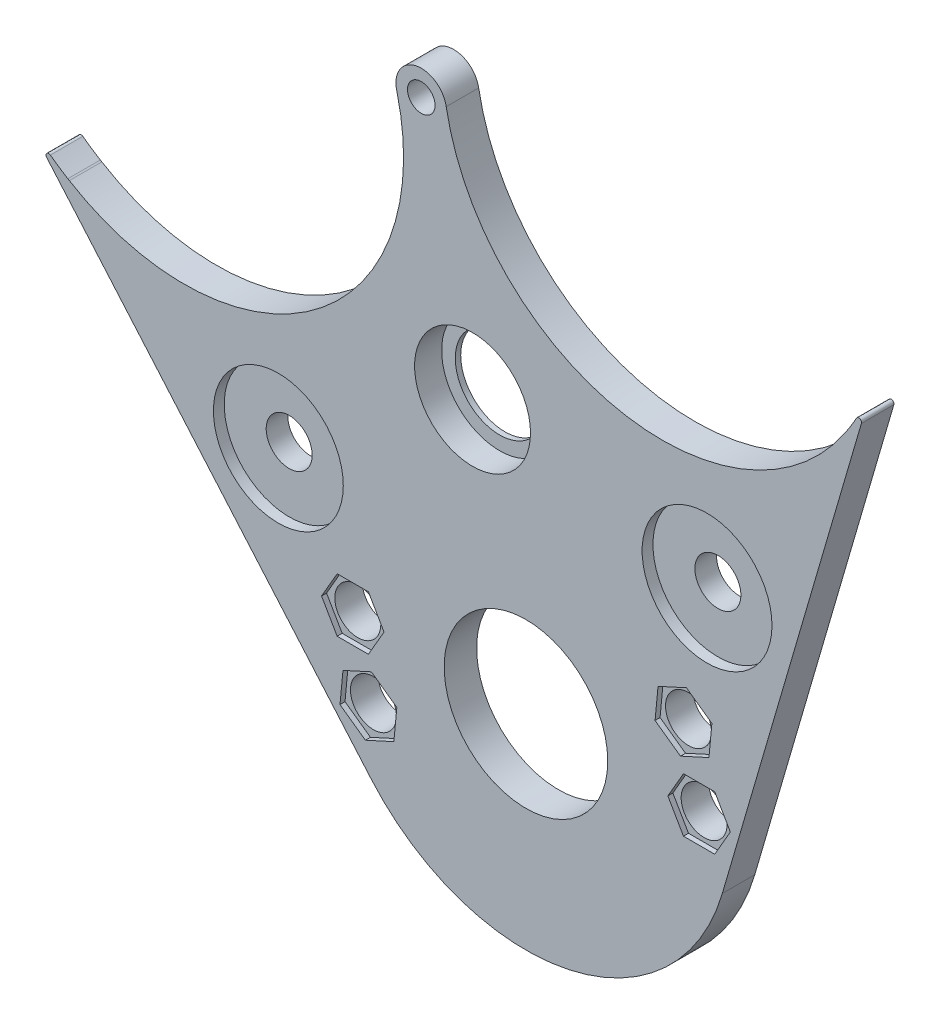
SolidWorks part; units mm, degrees
material "6061-T6 (SS)"
ref_plane "Front Plane" through (0, 0, 0) normal (0, 0, 1) x (1, 0, 0)
ref_plane "Top Plane" through (0, 0, 0) normal (0, 1, 0) x (1, 0, 0)
ref_plane "Right Plane" through (0, 0, 0) normal (1, 0, 0) x (0, 0, -1)
sketch "Sketch1" plane through (0, 0, 0) normal (0, 0, 1) x (1, 0, 0)
  line L0 (-7.8325, 36.0395) -> (0, 0) construction
  line L1 (-114.3559, 29.5275) -> (95.9028, 29.5275) construction
  line L2 (-107.2972, 26.9875) -> (95.9028, 26.9875) construction
  line L3 (-34.299, 122.3851) -> (-30.7317, 35.1036) construction
  line L4 (-107.2972, -23.8125) -> (95.9028, -23.8125) construction
  line L5 (-19.5919, 125.5814) -> (13.3895, 44.6925) construction
  line L6 (-55.9402, 56.7468) -> (-25.1916, 21.0759) construction
  line L7 (14.1715, 29.6307) -> (27.3408, 74.8464) construction
  line L8 (-50.1538, 61.7347) -> (-7.8325, 36.0395) construction
  line L9 (-7.8325, 36.0395) -> (-26.6659, 122.6971) construction
  line L10 (-7.8325, 36.0395) -> (20.0062, 76.9827) construction
  line L11 (-48.8132, 69.2556) -> (-16.6236, 63.5179) construction
  line L12 (-11.2396, 64.688) -> (15.6649, 83.2687) construction
  line L13 (0, 0) -> (-25.4, 0) construction
  line L14 (-26.6659, 122.6971) -> (-26.7738, 123.1935) construction
  line L15 (-50.1538, 61.7347) -> (-50.588, 61.9983) construction
  line L16 (-22.7158, -19.6015) -> (-74.972, 40.9574)
  line L17 (28.8025, -8.4049) -> (51.2095, 68.3806)
  line L18 (-51.5405, 117.551) -> (-1.8993, 128.3396) construction
  line L19 (-49.7306, 112.0585) -> (-3.6012, 133.3357) construction
  line L20 (-52.1736, 123.2992) -> (-1.374, 123.0877) construction
  line L21 (2.5906, 95.4721) -> (37.4217, 58.4932) construction
  line L22 (-58.3242, 37.6847) -> (-41.9834, 85.7847) construction
  line L23 (-68.1569, 43.6546) -> (-33.0191, 80.3421) construction
  line L24 (-37.1888, 83.5781) -> (-63.553, 40.155) construction
  line L25 (-50.588, 61.9983) -> (-47.8741, 60.3506) construction
  line L26 (-45.3152, 70.683) -> (-42.6012, 69.0352) construction
  line L27 (-55.8609, 53.3137) -> (-53.1469, 51.666) construction
  line L28 (-26.7738, 123.1935) -> (-26.0995, 120.0909) construction
  line L29 (-16.8456, 125.3512) -> (-16.1713, 122.2486) construction
  line L30 (-36.702, 121.0358) -> (-36.0278, 117.9332) construction
  line L31 (20.0062, 76.9827) -> (20.2918, 77.4027) construction
  line L32 (-0.8556, 91.4744) -> (41.1535, 62.911) construction
  line L33 (-3.306, 86.7997) -> (43.8896, 68.0058) construction
  line L34 (20.2918, 77.4027) -> (18.5066, 74.7772) construction
  line L35 (28.6936, 71.6901) -> (26.9084, 69.0645) construction
  line L36 (11.89, 83.1154) -> (10.1047, 80.4899) construction
  line L37 (0, 0) -> (25.4, 0) construction
  line L38 (0, 0) -> (-23.1088, -10.5425) construction
  line L39 (0, 0) -> (23.1088, 10.5425) construction
  line L41 (-29.9827, 0) -> (-27.6914, -3.9688)
  line L42 (-27.6914, -3.9688) -> (-23.1086, -3.9688)
  line L43 (-23.1086, -3.9688) -> (-20.8173, 0)
  line L44 (-20.8173, 0) -> (-23.1086, 3.9688)
  line L45 (-23.1086, 3.9688) -> (-27.6914, 3.9688)
  line L46 (-27.6914, 3.9688) -> (-29.9827, 0)
  line L47 (-18.9395, -8.6404) -> (-22.6714, -5.9807)
  line L48 (-22.6714, -5.9807) -> (-26.8407, -7.8828)
  line L49 (-26.8407, -7.8828) -> (-27.2781, -12.4446)
  line L50 (-27.2781, -12.4446) -> (-23.5462, -15.1043)
  line L51 (-23.5462, -15.1043) -> (-19.3769, -13.2022)
  line L52 (-19.3769, -13.2022) -> (-18.9395, -8.6404)
  line L53 (18.9395, 8.6404) -> (22.6714, 5.9807)
  line L54 (22.6714, 5.9807) -> (26.8407, 7.8828)
  line L55 (26.8407, 7.8828) -> (27.2781, 12.4446)
  line L56 (27.2781, 12.4446) -> (23.5462, 15.1043)
  line L57 (23.5462, 15.1043) -> (19.3769, 13.2022)
  line L58 (19.3769, 13.2022) -> (18.9395, 8.6404)
  line L59 (20.8173, 0) -> (23.1086, -3.9688)
  line L60 (23.1086, -3.9688) -> (27.6914, -3.9688)
  line L61 (27.6914, -3.9688) -> (29.9827, 0)
  line L62 (29.9827, 0) -> (27.6914, 3.9688)
  line L63 (27.6914, 3.9688) -> (23.1086, 3.9688)
  line L64 (23.1086, 3.9688) -> (20.8173, 0)
  circle A0 centre (0, 0) radius 27.94 construction
  circle A1 centre (-7.8325, 36.0395) radius 15.24 construction
  circle A2 centre (-7.8325, 36.0395) radius 8.89 construction
  circle A3 centre (0, 0) radius 21.59 construction
  circle A4 centre (-50.1538, 61.7347) radius 32.2072
  circle A5 centre (20.0062, 76.9827) radius 32.2072
  circle A6 centre (-26.6659, 122.6971) radius 32.2072 construction
  arc A7 (-25.1916, 21.0759) -> (14.1715, 29.6307) centre (-7.8325, 36.0395) ccw construction
  arc A8 (-48.8132, 69.2556) -> (-55.9402, 56.7468) centre (-50.1538, 61.7347) ccw construction
  arc A9 (27.3408, 74.8464) -> (15.6649, 83.2687) centre (20.0062, 76.9827) ccw construction
  arc A10 (-19.5919, 125.5814) -> (-34.299, 122.3851) centre (-26.6659, 122.6971) ccw construction
  circle A11 centre (-15.3533, 70.6445) radius 3.175 construction
  arc A12 (-16.6236, 63.5179) -> (-11.2396, 64.688) centre (-15.3533, 70.6445) ccw construction
  arc A13 (-30.7317, 35.1036) -> (13.3895, 44.6925) centre (-7.8325, 36.0395) ccw construction
  circle A14 centre (-26.7738, 123.1935) radius 32.2072 construction
  circle A15 centre (-26.7199, 122.9453) radius 32.2072 construction
  circle A16 centre (-50.588, 61.9983) radius 32.2072
  circle A17 centre (-50.3709, 61.8665) radius 32.2072
  arc A18 (5.4875, 124.5569) -> (20.9913, 109.6024) centre (21.336, 125.4736) ccw construction
  arc A19 (-64.5891, 91.0031) -> (-56.6909, 111.0436) centre (-71.4903, 105.2995) ccw construction
  circle A20 centre (-36.3191, 15.6028) radius 9.525
  circle A21 centre (26.5668, 29.2699) radius 9.525
  arc A22 (-22.7158, -19.6015) -> (28.8025, -8.4049) centre (0, 0) ccw
  circle A23 centre (-7.8325, 36.0395) radius 10.5 construction
  circle A24 centre (0, 0) radius 13 construction
  circle A25 centre (0, 0) radius 8.5 construction
  circle A26 centre (0, 0) radius 12
  circle A27 centre (-7.8325, 36.0395) radius 8.5
  arc A28 (-45.3152, 70.683) -> (-55.8609, 53.3137) centre (-50.588, 61.9983) ccw construction
  arc A29 (-53.1469, 51.666) -> (-42.6012, 69.0352) centre (-47.8741, 60.3506) ccw construction
  arc A30 (-16.8456, 125.3512) -> (-36.702, 121.0358) centre (-26.7738, 123.1935) ccw construction
  arc A31 (-36.0278, 117.9332) -> (-16.1713, 122.2486) centre (-26.0995, 120.0909) ccw construction
  arc A32 (28.6936, 71.6901) -> (11.89, 83.1154) centre (20.2918, 77.4027) ccw construction
  circle A33 centre (-15.3533, 70.6445) radius 3.7158
  arc A34 (-69.7639, 36.1219) -> (-70.3006, 35.5438) centre (-70.0002, 35.803) ccw
  circle A35 centre (20.149, 77.1927) radius 32.2072
  circle A36 centre (20.2918, 77.4027) radius 32.2072
  arc A37 (10.1047, 80.4899) -> (26.9084, 69.0645) centre (18.5066, 74.7772) ccw construction
  arc A38 (49.2064, 61.5164) -> (48.4781, 61.8196) centre (48.8254, 61.6276) ccw
  circle A39 centre (0, 0) radius 25.4 construction
  circle A40 centre (-25.4, 0) radius 3.9687 construction
  circle A41 centre (-23.1088, -10.5425) radius 3.9687 construction
  circle A42 centre (23.1088, 10.5425) radius 3.9687 construction
  circle A43 centre (25.4, 0) radius 3.9688 construction
  point P64 (-26.7199, 122.9453)
  point P66 (-51.5405, 117.551)
  point P67 (-1.8993, 128.3396)
  point P69 (-26.6659, 122.6971)
  point P71 (-49.7306, 112.0585)
  point P72 (-3.6012, 133.3357)
  point P74 (-26.7738, 123.1935)
  point P76 (-52.1736, 123.2992)
  point P77 (-1.374, 123.0877)
  point P79 (20.0062, 76.9827)
  point P81 (2.5906, 95.4721)
  point P82 (37.4217, 58.4932)
  point P88 (-50.588, 61.9983)
  point P89 (-68.1569, 43.6546)
  point P90 (-58.3242, 37.6847)
  point P91 (-63.553, 40.155)
  point P92 (-37.1888, 83.5781)
  point P93 (-41.9834, 85.7847)
  point P94 (-33.0191, 80.3421)
  point P95 (-50.3709, 61.8665)
  point P96 (-50.1538, 61.7347)
  point P98 (-49.231, 61.1745)
  point P104 (-26.4367, 121.6422)
  point P120 (20.149, 77.1927)
  point P121 (20.2918, 77.4027)
  point P122 (19.3992, 76.09)
  point P123 (-0.8556, 91.4744)
  point P124 (-3.306, 86.7997)
  point P125 (41.1535, 62.911)
  point P126 (43.8896, 68.0058)
  dimension "D1" = 55.88
  dimension "D2" = 43.18
  dimension "D3" = 17.78
  dimension "D4" = 30.48
  dimension "D10" = 64.4144
  dimension "D11" = 45.8366
  dimension "D12" = 15.2789
  dimension "D16" = 92.949
  dimension "D18" = 6.35
  dimension "D19" = 14.478
  dimension "D20" = 252
  dimension "D9" = 45.8366
  dimension "D23" = 0.254
  dimension "D22" = 276
  dimension "D25" = 31.75
  dimension "D26" = 30.0037
  dimension "D27" = 19.05
  dimension "D31" = 26
  dimension "D30" = 21
  dimension "D32" = 17
  dimension "D33" = 24
  dimension "D34" = 17
  dimension "D38" = 12.5
  dimension "D40" = 10.16
  dimension "D42" = 10.16
  dimension "D44" = 12.5
  dimension "D45" = 0.7937
  dimension "D49" = 10.16
  dimension "D50" = 0.7937
  dimension "D57" = 50.8
  dimension "D5" = 36.8808
  dimension "D6" = 26.9875
  dimension "D7" = 50.8
  dimension "D8" = 2.54
  dimension "D13" = 49.5109
  dimension "D14" = 49.5109
  dimension "D15" = 123
  dimension "D17" = 46.475
  dimension "D21" = 140.868
  dimension "D24" = 0.254
  dimension "D28" = 12.7
  dimension "D29" = 12.7
  dimension "D35" = 50.8
  dimension "D36" = 12.5
  dimension "D37" = 12.5
  dimension "D39" = 12.5
  dimension "D41" = 3.175
  dimension "D43" = 3.175
  dimension "D46" = 0.254
  dimension "D47" = 12.5
  dimension "D48" = 3.175
  dimension "D51" = 77.739
  dimension "D52" = 77.739
  dimension "D53" = 7.9375
  dimension "D54" = 7.9375
  dimension "D55" = 7.9375
  dimension "D56" = 7.9375
extrude "Boss-Extrude1" add sketch "Sketch1" against normal blind 4.7625 contours L17 A38 A36 A35 A5 A33 A4 A17 A16 A34 L16 A22 A20 A21 A26 A27 | A20 | A21 | A33 | L51 L52 L47 L48 L49 L50 | L45 L46 L41 L42 L43 L44 | L57 L58 L53 L54 L55 L56 | L63 L64 L59 L60 L61 L62 region at (-3.534, 16.2611, 0) region at (-15.3533, 70.6445, 0) region at (-25.4, 0, 0) region at (-23.1088, -10.5425, 0) region at (23.1088, 10.5425, 0) region at (25.4, 0, 0) region at (-36.3191, 15.6028, 0) region at (26.5668, 29.2699, 0)
extrude "Cut-Extrude1" cut sketch "Sketch1<4>" against normal blind 1.5875 contours A20 | A21 region at (-36.3191, 15.6028, 0) region at (26.5668, 29.2699, 0)
sketch "Sketch1<4>" plane through (0, 0, 0) normal (0, 0, 1) x (1, 0, 0) same geometry as "Sketch1"
hole_wizard "#10-32 Tapped Hole1" positions "Sketch3" profile "Sketch2" tap size "#10-32" standard "ANSI Inch" end condition through all
sketch "Sketch3" plane through (0, 0, 0) normal (0, 0, 1) x (1, 0, 0)
  point P0 (-15.3533, 70.6445)
sketch "Sketch2" plane through (-15.3533, 70.6445, 0) normal (1, 0, 0) x (0, -1, 0)
  line L0 (0, 0) -> (0, 4.7625)
  line L1 (0, 4.7625) -> (2.0193, 4.7625)
  line L2 (2.0193, 4.7625) -> (2.0193, 0)
  line L5 (2.0193, 0) -> (0, 0)
  line L11 (0, -6.35) -> (0, 107.95) construction
  dimension "Thru Tap Drill Dia." = 4.0386
  dimension "Thru Tap Drill Depth" = 4.7625
cosmetic thread "Hole Thread1" parameters "D2"=4.826
sketch "Sketch7" plane through (0, 0, -4.7625) normal (0, 0, -1) x (-1, 0, 0)
  circle A0 centre (7.8325, 36.0395) radius 8.5 construction
  circle A1 centre (7.8325, 36.0395) radius 8.5
  circle A2 centre (7.8325, 36.0395) radius 6.5
  dimension "D1" = 13
extrude "Boss-Extrude3" add sketch "Sketch7" against normal blind 0.7937
hole_wizard "17/64 (0.26563) Diameter Hole1" positions "Sketch9" profile "Sketch8" hole size "17/64" standard "ANSI Inch" end condition through all
sketch "Sketch9" plane through (0, 0, 0) normal (0, 0, 1) x (1, 0, 0)
  point P0 (-36.3191, 15.6028)
  point P3 (26.5668, 29.2699)
  point P6 (23.1088, 10.5425)
  point P9 (25.4, 0)
  point P12 (-23.1088, -10.5425)
  point P15 (-25.4, 0)
sketch "Sketch8" plane through (-36.3191, 15.6028, 0) normal (1, 0, 0) x (0, -1, 0)
  line L0 (0, 0) -> (0, 4.7625)
  line L1 (0, 4.7625) -> (3.3735, 4.7625)
  line L2 (3.3735, 4.7625) -> (3.3735, 0)
  line L5 (3.3735, 0) -> (0, 0)
  line L11 (0, -6.35) -> (0, 107.95) construction
  dimension "Thru Hole Dia." = 6.747
  dimension "Thru Hole Depth" = 4.7625
extrude "Cut-Extrude2" cut sketch "Sketch1<5>" against normal blind 0.7366 contours L45 L46 L41 L42 L43 L44 | L51 L52 L47 L48 L49 L50 | L57 L58 L53 L54 L55 L56 | L63 L64 L59 L60 L61 L62 region at (-25.4, 0, 0) region at (-23.1088, -10.5425, 0) region at (23.1088, 10.5425, 0) region at (25.4, 0, 0)
sketch "Sketch1<5>" plane through (0, 0, 0) normal (0, 0, 1) x (1, 0, 0) same geometry as "Sketch1"
equation "\"D1@Sketch1\"=44/20"
equation "\"D2@Sketch1\"=34/20"
equation "\"D3@Sketch1\"=14/20"
equation "\"D4@Sketch1\"=24/20"
equation "\"D5@Sketch1\"=(14+44)/20/2 + .002"
equation "\"D11@Sketch1\"=48*3mm/pi"
equation "\"D12@Sketch1\"=16*3mm/pi"
equation "\"D13@Sketch1\"=(\"D10@Sketch1\"+\"D4@Sketch1\"+.1)/2+1/32"
equation "\"D14@Sketch1\"=\"D13@Sketch1\""
equation "\"D16@Sketch1\"=\"D17@Sketch1\""
equation "\"D17@Sketch1\"=\"D16@Sketch1\"/2"
equation "\"D20@Sketch1\"=252mm"
equation "\"D19@Sketch1\"=0.50in+.035*2"
equation "\"D22@Sketch1\"=92*3mm"
equation "\"D9@Sketch1\"=\"D11@Sketch1\""
equation "\"D26@Sketch1\"=(46/20)/2+1/32"
equation "\"D31@Sketch1\"=26mm"
equation "\"D30@Sketch1\"=21mm"
equation "\"D32@Sketch1\"=17mm"
equation "\"D33@Sketch1\"=24mm"
equation "\"D34@Sketch1\"=17mm"
